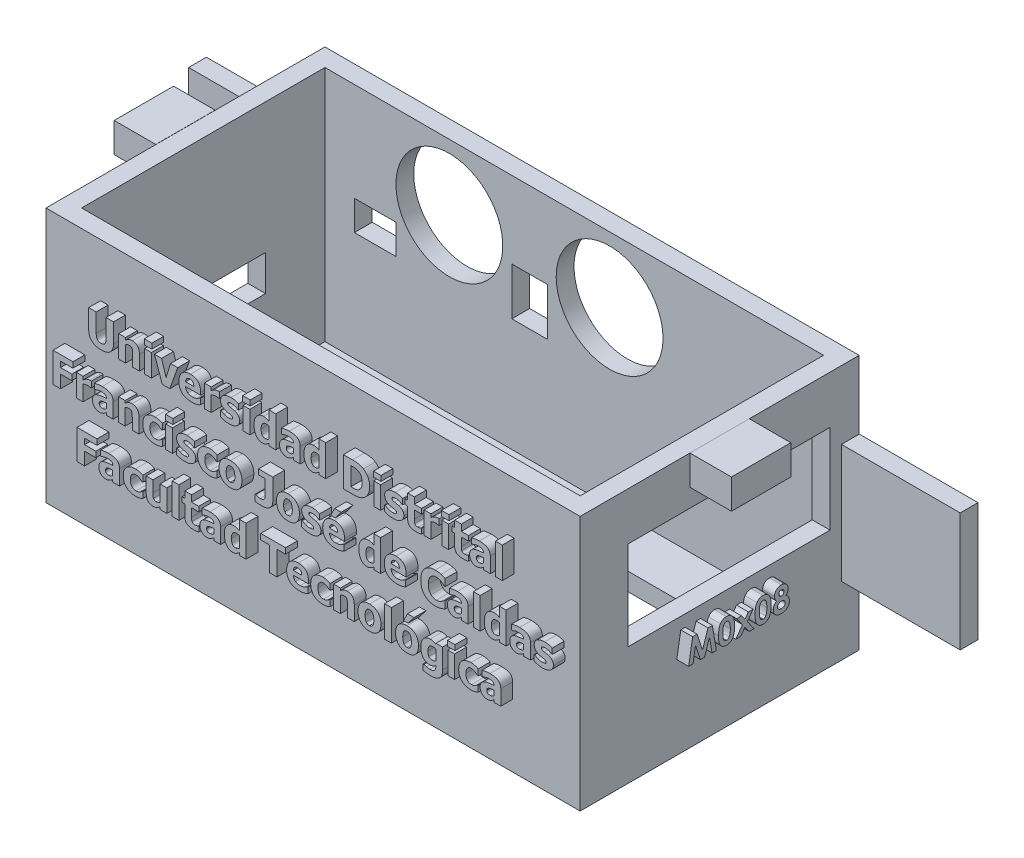
SolidWorks part; units mm, degrees
ref_plane "Alzado" through (0, 0, 0) normal (0, 0, 1) x (1, 0, 0)
ref_plane "Planta" through (0, 0, 0) normal (0, 1, 0) x (1, 0, 0)
ref_plane "Vista lateral" through (0, 0, 0) normal (1, 0, 0) x (0, 0, -1)
sketch "Croquis1" plane through (0, 0, 0) normal (0, 1, 0) x (1, 0, 0)
  line L1 (-45, 23.5) -> (45, 23.5)
  line L2 (-45, 23.5) -> (-45, -23.5)
  line L3 (-45, -23.5) -> (45, -23.5)
  line L4 (45, 23.5) -> (45, -23.5)
  line L5 (-45, 23.5) -> (45, -23.5) construction
  line L6 (-45, -23.5) -> (45, 23.5) construction
  point P0 (0, 0)
extrude "Saliente-Extruir1" add sketch "Croquis1" along normal blind 3
sketch "Croquis2" plane through (0, 3, 0) normal (0, 1, 0) x (1, 0, 0)
  line L1 (-42, 20.5) -> (42, 20.5)
  line L2 (-42, 20.5) -> (-42, -20.5)
  line L3 (-42, -20.5) -> (42, -20.5)
  line L4 (42, 20.5) -> (42, -20.5)
  line L5 (-42, 20.5) -> (42, -20.5) construction
  line L6 (-42, -20.5) -> (42, 20.5) construction
  line L9 (45, 23.5) -> (-45, 23.5) construction
  line L10 (-45, 23.5) -> (-45, -23.5) construction
  line L11 (45, -23.5) -> (45, 23.5) construction
  line L12 (-45, -23.5) -> (45, -23.5) construction
  line L13 (45, 23.5) -> (-45, 23.5)
  line L14 (-45, 23.5) -> (-45, -23.5)
  line L15 (45, -23.5) -> (45, 23.5)
  line L16 (-45, -23.5) -> (45, -23.5)
  point P0 (0, 0)
extrude "Saliente-Extruir2" add sketch "Croquis2" along normal blind 40
sketch "Croquis6" plane through (0, 0, 0) normal (0, -1, 0) x (-1, 0, 0)
  line L1 (36.0091, -12.4705) -> (-35.9909, -12.4705)
  line L2 (36.0091, -12.4705) -> (36.0091, 12.5295)
  line L3 (36.0091, 12.5295) -> (-35.9909, 12.5295)
  line L4 (-35.9909, -12.4705) -> (-35.9909, 12.5295)
extrude "Cortar-Extruir5" cut sketch "Croquis6" against normal blind 3
sketch "Croquis8" plane through (45, 0, 0) normal (1, 0, 0) x (0, 0, -1)
  line L5 (-15.4013, 34.9423) -> (18.5987, 34.9423)
  line L6 (-15.4013, 34.9423) -> (-15.4013, 19.9423)
  line L7 (-15.4013, 19.9423) -> (18.5987, 19.9423)
  line L8 (18.5987, 34.9423) -> (18.5987, 19.9423)
extrude "Cortar-Extruir6" cut sketch "Croquis8" against normal blind 3
sketch "Croquis9" plane through (45, 0, 0) normal (1, 0, 0) x (0, 0, -1)
  line L2 (-5.0086, 43.0022) -> (4.9914, 43.0022)
  line L3 (-5.0086, 43.0022) -> (-5.0086, 38.0022)
  line L4 (-5.0086, 38.0022) -> (4.9914, 38.0022)
  line L5 (4.9914, 43.0022) -> (4.9914, 38.0022)
extrude "Saliente-Extruir3" add sketch "Croquis9" along normal blind 7
sketch "Croquis10" plane through (45, 0, 0) normal (1, 0, 0) x (0, 0, -1)
  line L2 (20.5283, 31.4936) -> (23.5283, 31.4936)
  line L3 (20.5283, 31.4936) -> (20.5283, 11.4936)
  line L4 (20.5283, 11.4936) -> (23.5283, 11.4936)
  line L5 (23.5283, 31.4936) -> (23.5283, 11.4936)
extrude "Saliente-Extruir4" add sketch "Croquis10" along normal blind 20
sketch "Croquis12" plane through (-45, 0, 0) normal (-1, 0, 0) x (0, 0, 1)
  line L1 (-23.5294, 31.4856) -> (-20.5294, 31.4856)
  line L2 (-23.5294, 31.4856) -> (-23.5294, 11.4856)
  line L3 (-23.5294, 11.4856) -> (-20.5294, 11.4856)
  line L4 (-20.5294, 31.4856) -> (-20.5294, 11.4856)
extrude "Saliente-Extruir5" add sketch "Croquis12" along normal blind 20
sketch "Croquis13" plane through (-45, 0, 0) normal (-1, 0, 0) x (0, 0, 1)
  line L2 (-4.9927, 43.0287) -> (5.0073, 43.0287)
  line L3 (-4.9927, 43.0287) -> (-4.9927, 38.0287)
  line L4 (-4.9927, 38.0287) -> (5.0073, 38.0287)
  line L5 (5.0073, 43.0287) -> (5.0073, 38.0287)
extrude "Saliente-Extruir6" add sketch "Croquis13" along normal blind 7
sketch "Croquis14" plane through (-45, 0, 0) normal (-1, 0, 0) x (0, 0, 1)
  line L1 (-10.5011, 21.0075) -> (0.4989, 21.0075)
  line L2 (-10.5011, 21.0075) -> (-10.5011, 15.0075)
  line L3 (-10.5011, 15.0075) -> (0.4989, 15.0075)
  line L4 (0.4989, 21.0075) -> (0.4989, 15.0075)
  line L5 (-23.5, 43) -> (-23.5, 31.4856) construction
extrude "Cortar-Extruir8" cut sketch "Croquis14" against normal blind 3
sketch "Croquis15" plane through (0, 0, -23.5) normal (0, 0, -1) x (-1, 0, 0)
  line L14 (30.0381, 26.3981) -> (37.0381, 26.3981)
  line L15 (30.0381, 26.3981) -> (30.0381, 21.3981)
  line L16 (30.0381, 21.3981) -> (37.0381, 21.3981)
  line L17 (37.0381, 26.3981) -> (37.0381, 21.3981)
  line L20 (4.5108, 30.0753) -> (10.5108, 30.0753)
  line L21 (4.5108, 30.0753) -> (4.5108, 22.0753)
  line L22 (4.5108, 22.0753) -> (10.5108, 22.0753)
  line L23 (10.5108, 30.0753) -> (10.5108, 22.0753)
  circle A0 centre (-5.9583, 31.9461) radius 9
  circle A1 centre (21.0417, 31.9461) radius 9
  dimension "D1" = 5
extrude "Cortar-Extruir9" cut sketch "Croquis15" against normal blind 3
sketch "Croquis16" plane through (0, 0, 23.5) normal (0, 0, 1) x (1, 0, 0)
  text T0 "   Universidad Distrital\r\nFrancisco José de Caldas\r\n  Facultad Tecnológica" font "Tahoma" height 5
extrude "Saliente-Extruir7" add sketch "Croquis16" along normal blind 2
sketch "Croquis18" plane through (45, 0, 0) normal (1, 0, 0) x (0, 0, -1)
  text T0 "M0x08" font "Century Gothic" height 4
extrude "Saliente-Extruir10" add sketch "Croquis18" along normal blind 2
